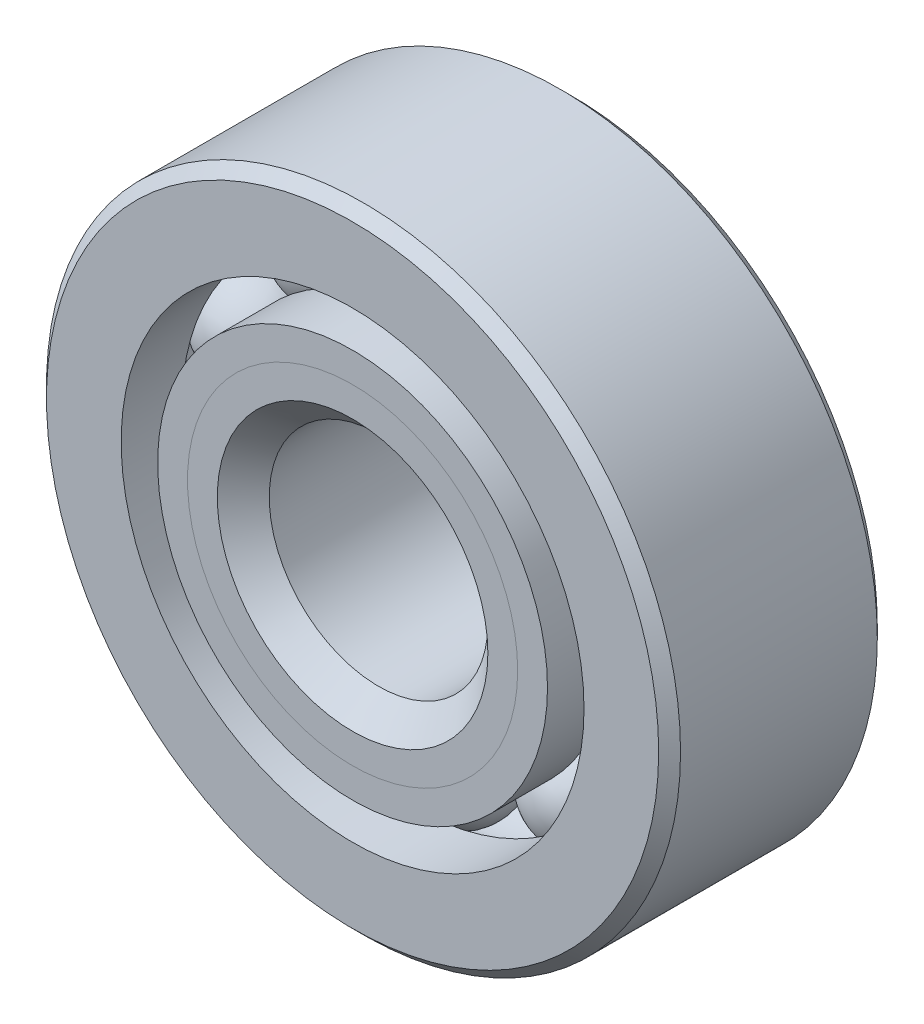
SolidWorks part; units mm, degrees
ref_plane "Front Plane" through (0, 0, 0) normal (0, 0, 1) x (1, 0, 0)
ref_plane "Top Plane" through (0, 0, 0) normal (0, 1, 0) x (1, 0, 0)
ref_plane "Right Plane" through (0, 0, 0) normal (1, 0, 0) x (0, 0, -1)
sketch "Sketch1" plane through (0, 0, 0) normal (1, 0, 0) x (0, 0, -1)
  line L0 (-3.9688, 0) -> (3.9688, 0) construction
  line L1 (0, 11.5094) -> (0, -11.5094) construction
  line L2 (3.5719, 11.5094) -> (-3.5719, 11.5094)
  line L3 (-3.5719, 11.5094) -> (-3.9688, 11.1125)
  line L4 (-3.9688, 11.1125) -> (-3.9688, 8.402)
  line L5 (-3.9688, 8.402) -> (-1.7639, 8.402)
  line L6 (3.9688, 8.402) -> (1.7639, 8.402)
  line L7 (3.9688, 11.1125) -> (3.9688, 8.402)
  line L8 (3.5719, 11.5094) -> (3.9688, 11.1125)
  line L9 (0, 11.5094) -> (0, 7.7391) construction
  line L10 (0, 7.7391) -> (0, 3.9688) construction
  arc A0 (-1.7639, 8.402) -> (1.7639, 8.402) centre (0, 7.7391) cw
  point P14 (0, 3.9688)
  dimension "Width" = 7.9375
  dimension "OD" = 23.0188
  dimension "D1" = 45
  dimension "D2" = 0.3969
  dimension "D3" = 3.5278
  dimension "D4" = 0.6629
revolve "Revolve1" add sketch "Sketch1" angle 360 about L0
sketch "Sketch2" plane through (0, 0, 0) normal (1, 0, 0) x (0, 0, -1)
  line L0 (-3.9688, 7.0762) -> (-1.7639, 7.0762)
  line L1 (-3.9688, 11.1125) -> (-3.9688, -11.1125) construction
  line L2 (-3.9688, 7.0762) -> (-3.9688, 5.9939)
  line L3 (-3.9688, 5.9939) -> (-2.8865, 4.9117)
  line L4 (-2.8865, 4.9117) -> (0, 4.9117)
  line L5 (0, 11.5094) -> (0, -11.5094) construction
  line L6 (0, 4.9117) -> (0, 5.8547)
  line L7 (0, 5.8547) -> (0, 3.9688) construction
  line L8 (-3.9688, 7.0762) -> (-3.9688, 4.9117) construction
  line L9 (-3.9688, 4.9117) -> (-2.8865, 4.9117) construction
  arc A0 (-1.7639, 7.0762) -> (0, 5.8547) centre (0, 7.7391) ccw
  arc A1 (1.7639, 8.402) -> (-1.7639, 8.402) centre (0, 7.7391) ccw construction
  circle A2 centre (0, 7.7391) radius 1.8843 construction
  dimension "D1" = 45
revolve "Revolve2" add sketch "Sketch2" angle 360 about L0
sketch "Sketch3" plane through (0, 0, 0) normal (1, 0, 0) x (0, 0, -1)
  line L0 (-3.9688, 5.9939) -> (-2.8865, 4.9117)
  line L1 (-2.8865, 4.9117) -> (0, 4.9117)
  line L2 (0, 4.9117) -> (0, 5.8547)
  line L3 (-3.9688, 5.9939) -> (-3.9688, 4.9117)
  line L4 (-3.9688, 7.0762) -> (-3.9688, 4.9117) construction
  line L5 (-3.9688, 4.9117) -> (-3.0258, 3.9688)
  line L6 (-3.0258, 3.9688) -> (3.5719, 3.9688)
  line L7 (3.5719, 11.5094) -> (3.5719, -11.5094) construction
  line L8 (3.5719, 3.9688) -> (3.9688, 4.3656)
  line L9 (3.9688, -11.1125) -> (3.9688, 11.1125) construction
  line L10 (3.9688, 4.3656) -> (3.9688, 7.0762)
  line L11 (3.9688, 7.0762) -> (1.7639, 7.0762)
  line L13 (3.5719, 11.5094) -> (3.9688, 11.1125) construction
  circle A0 centre (0, 7.7391) radius 1.8843 construction
  arc A1 (1.7639, 7.0762) -> (0, 5.8547) centre (0, 7.7391) cw
revolve "Revolve3" add sketch "Sketch3" angle 360 about L0
sketch "Sketch4" plane through (0, 0, 0) normal (1, 0, 0) x (0, 0, -1)
  line L0 (-1.8843, 7.7391) -> (1.8843, 7.7391)
  circle A1 centre (0, 7.7391) radius 1.8843 construction
  arc A2 (-1.8843, 7.7391) -> (1.8843, 7.7391) centre (0, 7.7391) cw
  arc A3 (1.7639, 8.402) -> (-1.7639, 8.402) centre (0, 7.7391) ccw construction
revolve "Revolve4" add sketch "Sketch4" angle 360 about L0
ref_axis "Axis1" through (0, 0, -3.9688) along (0, 0, 1)
pattern_circular "CirPattern1" count 10 every 36 about axis through (0, 0, -3.9688) along (0, 0, 1) of bodies 104
equation "\"D2@Sketch1\" = \"Width@Sketch1\"*.05"
equation "\"D3@Sketch1\" = \"Width@Sketch1\"/2.25"
equation "\"D4@Sketch1\" = (((\"OD@Sketch1\"-\"Width@Sketch1\")/2)/3.25)/3.5"
equation "\"D2@CirPattern1\" = 360/\"Balls@CirPattern1\""
